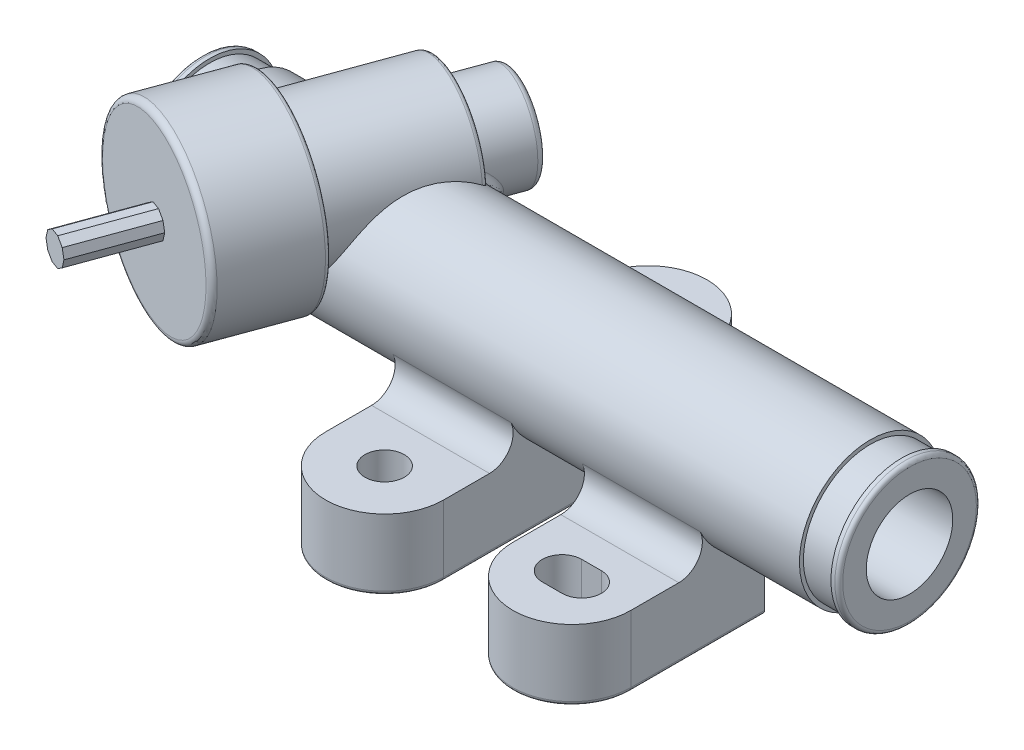
SolidWorks part; units mm, degrees
material "Alloy Steel"
ref_plane "Front Plane" through (0, 0, 0) normal (0, 0, 1) x (1, 0, 0)
ref_plane "Top Plane" through (0, 0, 0) normal (0, 1, 0) x (1, 0, 0)
ref_plane "Right Plane" through (0, 0, 0) normal (1, 0, 0) x (0, 0, -1)
sketch "Sketch1" plane through (0, 0, 0) normal (1, 0, 0) x (0, 0, -1)
  circle A0 centre (0, 0) radius 11
  circle A1 centre (0, 0) radius 18
  dimension "D1" = 22
  dimension "D2" = 36
extrude "Boss-Extrude1" add sketch "Sketch1" along normal blind 180
ref_plane "Plane1" through (0, -18, 0) normal (0, 1, 0) x (1, 0, 0)
sketch "Sketch2" plane through (0, -18, 0) normal (0, 1, 0) x (1, 0, 0)
  line L0 (80, 33.5) -> (80, -33.5)
  line L1 (0, 18) -> (0, -18) construction
  line L2 (0, 0) -> (124.4097, 0)
  line L3 (113.1301, -34.0071) -> (113.1301, 0)
  line L6 (80, 33.5) -> (80, -33.5) construction
  line L7 (95, 33.5) -> (95, -33.5)
  line L8 (65, 33.5) -> (65, -33.5)
  line L14 (125.6301, -34.0071) -> (130.6301, -34.0071) construction
  line L15 (125.6301, -39.0071) -> (130.6301, -39.0071)
  line L16 (125.6301, -29.0071) -> (130.6301, -29.0071)
  line L17 (113.1301, 0) -> (143.1301, 0)
  line L18 (143.1301, 0) -> (143.1301, -34.0071)
  circle A0 centre (80, 33.5) radius 5
  circle A1 centre (80, -33.5) radius 5
  arc A5 (95, 33.5) -> (65, 33.5) centre (80, 33.5) ccw
  arc A6 (65, -33.5) -> (95, -33.5) centre (80, -33.5) ccw
  arc A9 (125.6301, -39.0071) -> (125.6301, -29.0071) centre (125.6301, -34.0071) cw
  arc A10 (130.6301, -29.0071) -> (130.6301, -39.0071) centre (130.6301, -34.0071) cw
  arc A14 (113.1301, -34.0071) -> (143.1301, -34.0071) centre (128.1301, -34.0071) ccw
  point P9 (80, 0)
  point P33 (128.1301, -34.0071)
  dimension "D1" = 67
  dimension "D2" = 10
  dimension "D3" = 10
  dimension "D6" = 30
  dimension "D7" = 15
  dimension "D4" = 80
  dimension "D5" = 33.5
extrude "Boss-Extrude2" add sketch "Sketch2" against normal blind 16 and the other way blind 2 contours A10 L16 A9 L15 | A14 L18 L17 L3 | L8 A6 L7 A5 | A0 | A1 region at (128.1301, -18, 34.0071)
sketch "Sketch3" plane through (180, 0, 0) normal (1, 0, 0) x (0, 0, -1)
  circle A0 centre (0, 0) radius 11
extrude "Cut-Extrude1" [suppressed] cut sketch "Sketch3" against normal through all
ref_plane "Plane2" through (50, 0, 0) normal (-1, 0, 0) x (0, 0, 1)
sketch "Sketch4" plane through (50, 0, 0) normal (-1, 0, 0) x (0, 0, 1)
  line L0 (0, 0) -> (0, 8.423)
ref_plane "Plane3" through (5.8489, 0, -16.0697) normal (-0.342, 0, 0.9397) x (0, 1, 0)
sketch "Sketch5" plane through (5.8489, 0, -16.0697) normal (-0.342, 0, 0.9397) x (0, 1, 0)
  circle A0 centre (13.0934, -37.4923) radius 17.5
  dimension "D1" = 35
extrude "Boss-Extrude3" add sketch "Sketch5" along normal blind 20 and the other way blind 14
sketch "Sketch6" plane through (-0.9915, 0, 2.7242) normal (-0.342, 0, 0.9397) x (0.9397, 0, 0.342)
  circle A0 centre (37.4923, 13.0934) radius 23.5
  dimension "D1" = 47
extrude "Boss-Extrude4" add sketch "Sketch6" along normal blind 24
sketch "Sketch7" plane through (10.6372, 0, -29.2254) normal (0.342, 0, -0.9397) x (-0.9397, 0, -0.342)
  circle A0 centre (-37.4923, 13.0934) radius 12
  dimension "D1" = 24
extrude "Boss-Extrude5" add sketch "Sketch7" along normal blind 14
fillet "Fillet2" [suppressed] radius 10
sketch "Sketch8" plane through (-9.2, 0, 25.2768) normal (-0.342, 0, 0.9397) x (0.9397, 0, 0.342)
  line L1 (41.9107, 13.5097) -> (41.1827, 15.7501)
  line L2 (41.1827, 15.7501) -> (39.277, 17.1347)
  line L3 (39.277, 17.1347) -> (36.9213, 17.1347)
  line L4 (36.9213, 17.1347) -> (35.0155, 15.7501)
  line L5 (35.0155, 15.7501) -> (34.2876, 13.5097)
  line L6 (34.2876, 13.5097) -> (35.0155, 11.2694)
  line L7 (35.0155, 11.2694) -> (36.9213, 9.8847)
  line L8 (36.9213, 9.8847) -> (39.277, 9.8847)
  line L9 (39.277, 9.8847) -> (41.1827, 11.2694)
  line L10 (41.1827, 11.2694) -> (41.9107, 13.5097)
  circle A0 centre (38.0991, 13.5097) radius 3.625 construction
extrude "Boss-Extrude6" add sketch "Sketch8" along normal blind 20
sketch "Sketch9" plane through (0, 0, 0) normal (0, 1, 0) x (1, 0, 0)
  line L0 (0, -18) -> (12.5802, -18) construction
  line L1 (2, -18) -> (10, -18)
  line L2 (2, -18) -> (2, -17)
  line L3 (2, -17) -> (10, -17)
  line L4 (10, -18) -> (10, -17)
  line L5 (180, -18) -> (180, 18) construction
  line L6 (178, -18) -> (170, -18)
  line L7 (178, -18) -> (178, -17)
  line L8 (178, -17) -> (170, -17)
  line L9 (170, -18) -> (170, -17)
  line L10 (0, 18) -> (0, -18) construction
  dimension "D1" = 1
  dimension "D2" = 8
  dimension "D3" = 1
  dimension "D4" = 8
  dimension "D5" = 2
  dimension "D6" = 2
revolve "Cut-Revolve1" cut sketch "Sketch9" angle 360 about axis through (180, 0, 0) along (-1, 0, 0)
fillet "Fillet3" radius 1.5 5 edges at (54.3231, 3.7529, -17.6044) (39.4915, 22.9903, -18.7233) (39.3803, 13.0934, -33.6622) (48.114, 13.0934, 46.1374) (44.3436, 26.9005, 19.2248)
fillet "Fillet4" radius 1 11 edges at (95, -34, 0) (65, -34, 0) (113.1301, -34, 17.0036) (143.1301, -34, 17.0036) (34.8327, 26.0675, -20.4189) (51.5798, 27.6446, 21.8585) (0, 0, -18) (80, -34, -48.5) (180, 0, -18) (128.1301, -34, 49.0071) (80, -34, 48.5)
fillet "Fillet5" radius 6 3 edges at (128.1301, -16, 8.2462) (80, -16, -8.2462) (80, -16, 8.2462)
sketch "Sketch10" plane through (0, 0, 0) normal (-1, 0, 0) x (0, 0, 1)
  circle A0 centre (0, 0) radius 11
  circle A2 centre (0, 0) radius 11 construction
extrude "Cut-Extrude2" cut sketch "Sketch10" against normal blind 100
sketch3d "3DSketch1"
  line L0 (180, 0, 0) -> (0, 0, 0) construction
  point P0 (90, 0, 0)
